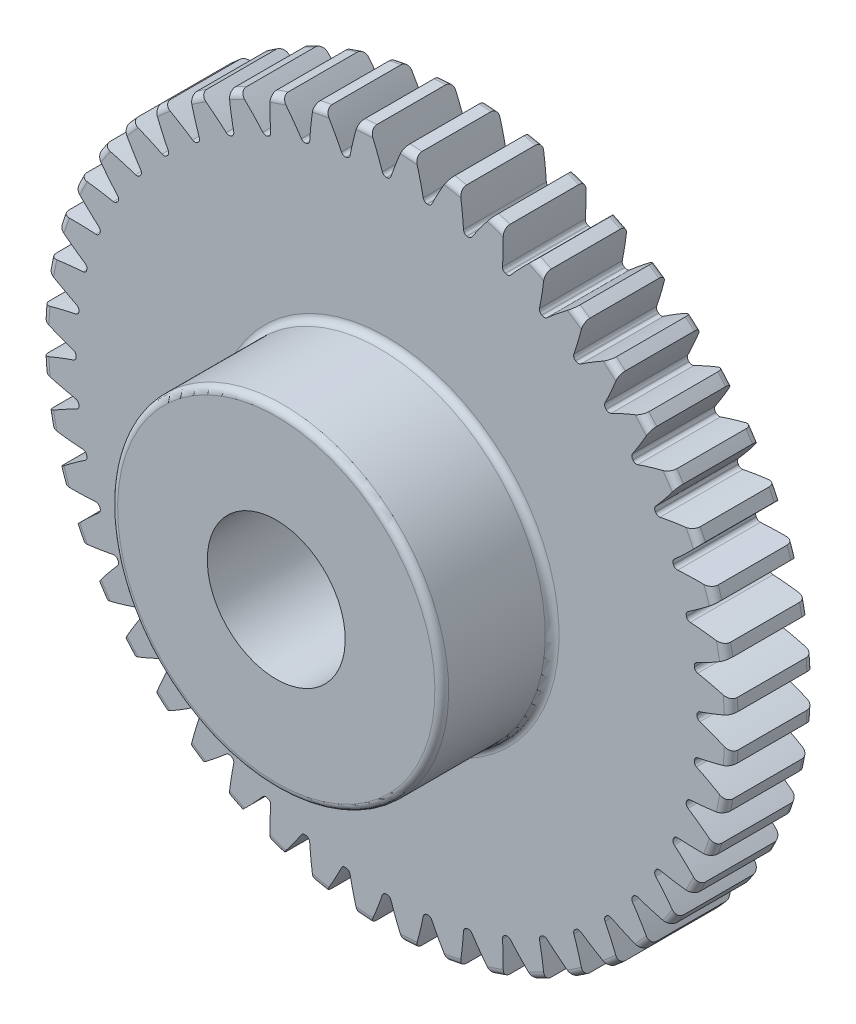
SolidWorks part; units mm, degrees
ref_plane "Front Plane" through (0, 0, 0) normal (0, 0, 1) x (1, 0, 0)
ref_plane "Top Plane" through (0, 0, 0) normal (0, 1, 0) x (1, 0, 0)
ref_plane "Right Plane" through (0, 0, 0) normal (1, 0, 0) x (0, 0, -1)
sketch "Sketch1" plane through (0, 0, 0) normal (0, 0, 1) x (1, 0, 0)
  line L0 (-609.6, 0) -> (609.6, 0) construction
  circle A0 centre (0, 0) radius 12.5 construction
  circle A1 centre (0, 0) radius 12 construction
  circle A2 centre (0, 0) radius 11.25 construction
  circle A3 centre (0, 0) radius 6 construction
  circle A4 centre (0, 0) radius 2.5 construction
  dimension "D2" = 0.5
  dimension "D3" = 1.25
  dimension "D1" = 1.25
sketch "Sketch2" plane through (0, 0, 0) normal (1, 0, 0) x (0, 0, -1)
  line L0 (0, 0) -> (-3, 0) construction
  line L1 (-3, 0) -> (-7, 0) construction
  dimension "Overall Width" = 7
  dimension "Face Width" = 3
sketch "Sketch4" plane through (0, 0, 0) normal (1, 0, 0) x (0, 0, -1)
  line L0 (-7, 2.5) -> (-7, 6)
  line L1 (-7, 6) -> (-3, 6)
  line L2 (-3, 6) -> (-3, 12.5)
  line L3 (-3, 12.5) -> (0, 12.5)
  line L4 (0, 12.5) -> (0, 2.5)
  line L5 (-3, 6) -> (-3, 0) construction
  line L6 (0, 12.5) -> (0, -12.5) construction
  line L7 (-3, 6) -> (0, 6) construction
  line L12 (-7, 2.5) -> (0, 2.5)
revolve "Revolve1" add sketch "Sketch4" angle 360 about L1
fillet "Fillet2" radius 0.25 4 edges at (0, 6, 7) (0, 6, 3) (0, 12.5, 3) (0, 12.5, 0)
sketch "Sketch7" plane through (0, 0, 3) normal (0, 0, 1) x (1, 0, 0)
  line L0 (0, 0) -> (0, 12.5) construction
  line L1 (0.3926, 11.9936) -> (0.5904, 12.4861) construction
  line L3 (0.8175, 12.4732) -> (0.7848, 11.9743) construction
  line L4 (0.7848, 11.9743) -> (0.7358, 11.2259) construction
  line L5 (0, 0) -> (0.7358, 11.2259) construction
  line L6 (0.3926, 11.9936) -> (0, 0) construction
  line L7 (0.3926, 11.9936) -> (0.409, 12.4933) construction
  line L8 (0.3926, 11.9936) -> (0, 0) construction
  circle A0 centre (0, 0) radius 12.5 construction
  arc A1 (-0.0137, 11.25) -> (0.0137, 11.25) centre (0, 0) cw
  circle A2 centre (0, 0) radius 11.25 construction
  arc A3 (-0.3926, 11.9936) -> (0.3926, 11.9936) centre (0, 0) cw construction
  circle A4 centre (0, 0) radius 12 construction
  arc A5 (1.0319, 12.4573) -> (0.603, 12.4854) centre (0, 0) ccw construction
  arc A6 (0.3926, 11.9936) -> (1.1762, 11.9422) centre (0, 0) cw construction
  arc A7 (-0.603, 12.4854) -> (0.603, 12.4854) centre (0, 0) cw
  arc A8 (0.1561, 11.3521) -> (0.603, 12.4854) centre (11.5286, 7.5226) cw
  arc A9 (-0.1561, 11.3521) -> (-0.603, 12.4854) centre (-11.5286, 7.5226) ccw
  arc A10 (-0.0137, 11.25) -> (-0.1561, 11.3521) centre (-0.0139, 11.4) cw
  arc A11 (0.0137, 11.25) -> (0.1561, 11.3521) centre (0.0139, 11.4) ccw
  point P26 (-0.122, 11.2493)
  point P29 (0.122, 11.2493)
  dimension "D4" = 0.15
  dimension "D5" = 12
  dimension "D3" = 20
  dimension "D1" = 1.5708
  dimension "D2" = 0.7854
extrude "Cut-Extrude2" cut sketch "Sketch7" against normal through all
pattern_circular "CirPattern1" count 48 over 360 about axis through (0, 0, 7) along (0, 0, -1) of "Cut-Extrude2"
equation "\"D1@Sketch1\"=2.5*(\"Pitch Dia.@Sketch1\"/\"Number of Teeth@Sketch1\")"
equation "\"D1@CirPattern1\"=\"Number of Teeth@Sketch1\""
equation "\"D1@Fillet2\"=\"OD@Sketch1\"*.01"
equation "\"D1@Sketch7\"=3.14159*(\"Pitch Dia.@Sketch1\"/\"Number of Teeth@Sketch1\")"
equation "\"D2@Sketch7\"=\"D1@Sketch7\"/2"
equation "\"D4@Sketch7\"=\"D1@Sketch7\"*.0955"
equation "\"D5@Sketch7\"=\"Pitch Dia.@Sketch1\"/2"
